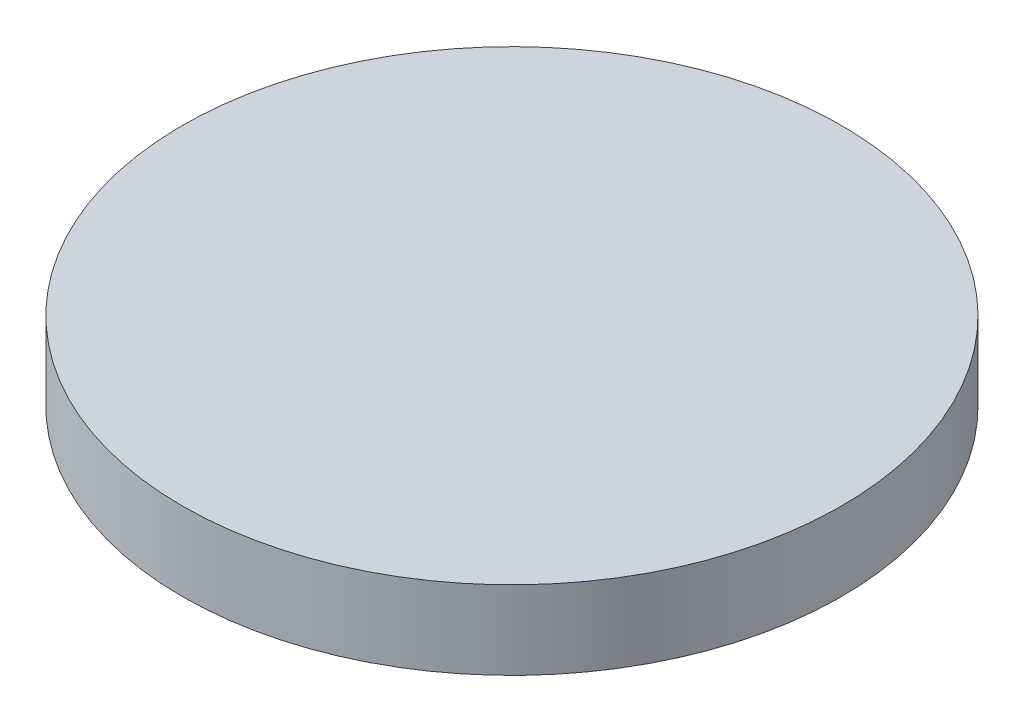
SolidWorks part; units mm, degrees
ref_plane "Front Plane" through (0, 0, 0) normal (0, 0, 1) x (1, 0, 0)
ref_plane "Top Plane" through (0, 0, 0) normal (0, 1, 0) x (1, 0, 0)
ref_plane "Right Plane" through (0, 0, 0) normal (1, 0, 0) x (0, 0, -1)
sketch "Sketch1" plane through (0, 0, 0) normal (0, 1, 0) x (1, 0, 0)
  circle A0 centre (0, 0) radius 21
  dimension "D1" = 42
extrude "Boss-Extrude1" add sketch "Sketch1" against normal blind 5
sketch "Sketch2" plane through (0, -5, 0) normal (0, -1, 0) x (1, 0, 0)
  circle A0 centre (0, 0) radius 4.863
  dimension "D1" = 9.726
extrude "Boss-Extrude2" add sketch "Sketch2" along normal blind 7
sketch "Sketch8" plane through (0, 0, 0) normal (0, 0, 1) x (1, 0, 0)
  line L0 (0, 0) -> (0, -12) construction
  line L1 (-4.863, -12) -> (4.863, -12) construction
sketch "Sketch9" plane through (0, -12, 0) normal (0, -1, 0) x (1, 0, 0)
  circle A0 centre (0, 0) radius 6
  dimension "D1" = 12
curve "Helix/Spiral1" pitch 1.75 height 7 radius 6 left hand yes centre (0, -12, 0) axis (0, 1, 0) start towards (1, 0, 0)
sketch "Sketch11" plane through (0, 0, 0) normal (0, 0, 1) x (1, 0, 0)
  line L0 (4.8262, -5) -> (4.8262, -5.7659)
  line L1 (-4.863, -5) -> (4.863, -5) construction
  line L2 (4.8262, -5.7659) -> (5.9632, -5.1095)
  line L3 (5.9632, -5.1095) -> (5.9632, -4.8905)
  line L4 (5.9632, -4.8905) -> (4.8262, -4.2341)
  line L5 (4.8262, -4.2341) -> (4.8262, -5)
  line L6 (4.8262, -5) -> (5.9632, -5) construction
  point P4 (4.8262, -5)
  point P9 (0, 0)
  point P10 (0, 0)
  dimension "D1" = 1.137
  dimension "D2" = 0.219
  dimension "D3" = 60
sweep "Sweep1" add profiles "Sketch11" path "Helix/Spiral1"
sketch "Sketch12" plane through (0, 0, 0) normal (0, 0, 1) x (1, 0, 0)
  line L0 (-4.863, -12) -> (4.863, -12) construction
  line L1 (0, -12) -> (5.9632, -12)
  line L2 (0, -12.7659) -> (0, -12) construction
  line L3 (0, -12.7659) -> (5.9632, -12.7659)
  line L4 (5.9632, -12) -> (5.9632, -12.7659)
  line L6 (0, -12.7659) -> (-4.863, -12.7659)
  line L8 (0, -12) -> (-4.863, -12)
  line L9 (-4.863, -12.7659) -> (-4.863, -12)
  point P8 (0, 0)
  point P10 (0, 0)
extrude "Cut-Extrude1" cut sketch "Sketch12" against normal through all both and the other way through all
